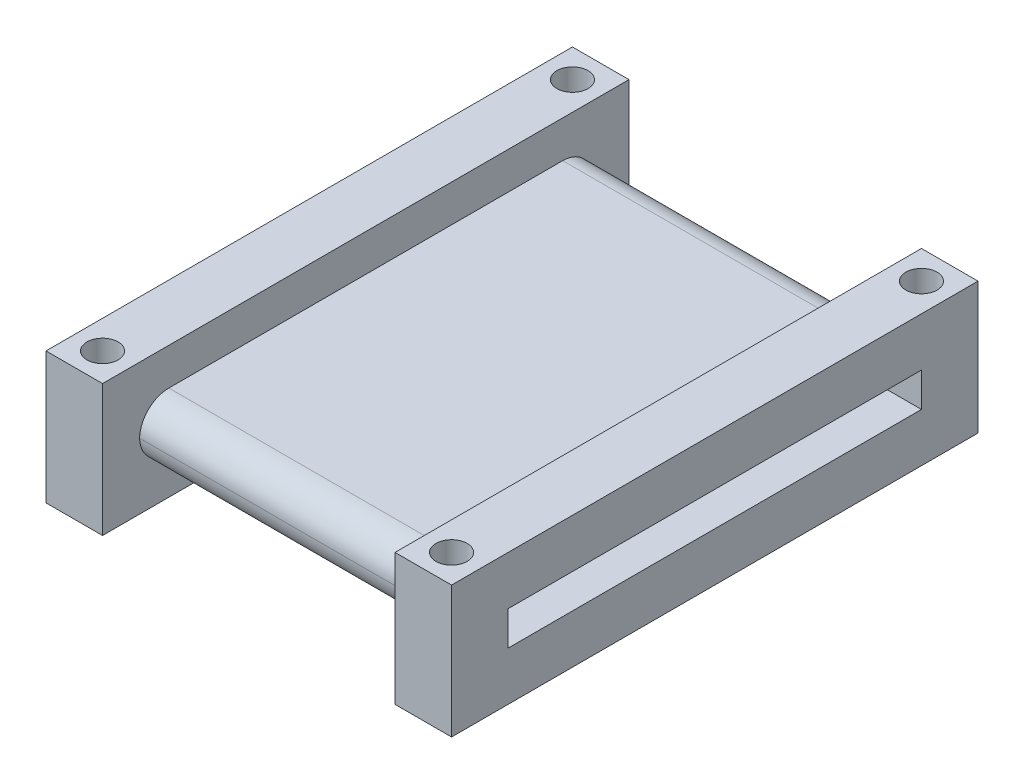
SolidWorks part; units mm, degrees
ref_plane "Front Plane" through (0, 0, 0) normal (0, 0, 1) x (1, 0, 0)
ref_plane "Top Plane" through (0, 0, 0) normal (0, 1, 0) x (1, 0, 0)
ref_plane "Right Plane" through (0, 0, 0) normal (1, 0, 0) x (0, 0, -1)
sketch "Sketch1" plane through (0, 0, 0) normal (1, 0, 0) x (0, 0, -1)
  line L0 (23.2, 5.9) -> (23.2, 0) construction
  line L1 (0, 0) -> (46.4, 0)
  line L2 (0, 0) -> (0, 5.9)
  line L3 (0, 5.9) -> (46.4, 5.9)
  line L4 (46.4, 0) -> (46.4, 5.9)
  line L6 (2, 1.2) -> (44.4, 1.2)
  line L7 (2, 1.2) -> (2, 4.7)
  line L8 (2, 4.7) -> (44.4, 4.7)
  line L9 (44.4, 1.2) -> (44.4, 4.7)
  line L10 (2, 1.2) -> (44.4, 4.7) construction
  line L11 (2, 4.7) -> (44.4, 1.2) construction
  point P7 (23.2, 2.95)
  dimension "D1" = 46.4
  dimension "D2" = 5.9
  dimension "D3" = 3.5
  dimension "D4" = 42.4
extrude "Boss-Extrude1" add sketch "Sketch1" along normal blind 30
fillet "Fillet2" radius 3 4 edges at (15, 0, -46.4) (15, 0, 0) (15, 5.9, 0) (15, 5.9, -46.4)
sketch "Sketch2" plane through (30, 0, 0) normal (1, 0, 0) x (0, 0, -1)
  line L0 (23.2, 5.9) -> (23.2, 0) construction
  line L1 (43.4, 5.9) -> (3, 5.9) construction
  line L2 (3, 0) -> (43.4, 0) construction
  line L4 (-3.8, -3.8) -> (50.2, -3.8)
  line L5 (-3.8, -3.8) -> (-3.8, 9.7)
  line L6 (-3.8, 9.7) -> (50.2, 9.7)
  line L7 (50.2, -3.8) -> (50.2, 9.7)
  line L8 (-3.8, -3.8) -> (50.2, 9.7) construction
  line L9 (-3.8, 9.7) -> (50.2, -3.8) construction
  line L14 (44.4, 1.2) -> (2, 1.2)
  line L15 (44.4, 1.2) -> (44.4, 4.7)
  line L16 (44.4, 4.7) -> (2, 4.7)
  line L17 (2, 1.2) -> (2, 4.7)
  line L18 (44.4, 1.2) -> (2, 4.7) construction
  line L19 (44.4, 4.7) -> (2, 1.2) construction
  point P6 (23.2, 2.95)
  point P11 (23.2, 2.95)
  point P12 (23.2, 2.95)
  dimension "D1" = 13.5
  dimension "D2" = 54
extrude "Boss-Extrude2" add sketch "Sketch2" along normal blind 5.8
sketch "Sketch3" plane through (0, 0, 0) normal (-1, 0, 0) x (0, 0, 1)
  line L0 (-23.2, 5.9) -> (-23.2, 0) construction
  line L1 (-43.4, 5.9) -> (-3, 5.9) construction
  line L2 (-3, 0) -> (-43.4, 0) construction
  line L4 (3.8, -3.8) -> (-50.2, -3.8)
  line L5 (3.8, -3.8) -> (3.8, 9.7)
  line L6 (3.8, 9.7) -> (-50.2, 9.7)
  line L7 (-50.2, -3.8) -> (-50.2, 9.7)
  line L8 (3.8, -3.8) -> (-50.2, 9.7) construction
  line L9 (3.8, 9.7) -> (-50.2, -3.8) construction
  line L10 (-2, 1.2) -> (-44.4, 1.2)
  line L11 (-2, 1.2) -> (-2, 4.7)
  line L12 (-2, 4.7) -> (-44.4, 4.7)
  line L13 (-44.4, 1.2) -> (-44.4, 4.7)
  line L14 (-2, 1.2) -> (-44.4, 4.7) construction
  line L15 (-2, 4.7) -> (-44.4, 1.2) construction
  point P6 (-23.2, 2.95)
  point P12 (-23.2, 2.95)
extrude "Boss-Extrude3" add sketch "Sketch3" along normal blind 5.8
sketch "Sketch4" plane through (0, 9.7, 0) normal (0, 1, 0) x (1, 0, 0)
  line L0 (-2.9, 50.2) -> (-2.9, 47.3) construction
  line L1 (-5.8, 50.2) -> (0, 50.2) construction
  line L2 (32.9, 50.2) -> (32.9, 47.3) construction
  line L3 (35.8, 50.2) -> (30, 50.2) construction
  line L4 (-2.9, -3.8) -> (-2.9, -0.9) construction
  line L5 (-5.8, -3.8) -> (0, -3.8) construction
  line L6 (32.9, -3.8) -> (32.9, -0.9) construction
  line L7 (35.8, -3.8) -> (30, -3.8) construction
  circle A0 centre (-2.9, 47.3) radius 1.6
  circle A1 centre (32.9, 47.3) radius 1.6
  circle A2 centre (-2.9, -0.9) radius 1.6
  circle A3 centre (32.9, -0.9) radius 1.6
  dimension "D2" = 3.2
  dimension "D4" = 3.2
  dimension "D6" = 3.2
  dimension "D8" = 3.2
  dimension "D1" = 2.9
  dimension "D3" = 2.9
  dimension "D5" = 2.9
  dimension "D7" = 2.9
extrude "Cut-Extrude1" cut sketch "Sketch4" against normal through all
sketch "Sketch6" plane through (35.8, 0, 0) normal (1, 0, 0) x (0, 0, -1)
  line L0 (50.2, -3.8) -> (50.2, 9.7) construction
  line L1 (-3.8, -3.8) -> (50.2, -3.8)
  line L2 (-3.8, -3.8) -> (-3.8, 3.4)
  line L3 (-3.8, 3.4) -> (50.2, 3.4)
  line L4 (50.2, -3.8) -> (50.2, 3.4)
  dimension "D1" = 7.2
extrude "Cut-Extrude2" [suppressed] cut sketch "Sketch6" against normal blind 5.8
sketch "Sketch7" plane through (-5.8, 0, 0) normal (-1, 0, 0) x (0, 0, 1)
  line L0 (3.8, -3.8) -> (3.8, 9.7) construction
  line L1 (-50.2, -3.8) -> (3.8, -3.8)
  line L2 (-50.2, -3.8) -> (-50.2, 3.4)
  line L3 (-50.2, 3.4) -> (3.8, 3.4)
  line L4 (3.8, -3.8) -> (3.8, 3.4)
  dimension "D1" = 7.2
extrude "Cut-Extrude3" [suppressed] cut sketch "Sketch7" against normal blind 5.8
